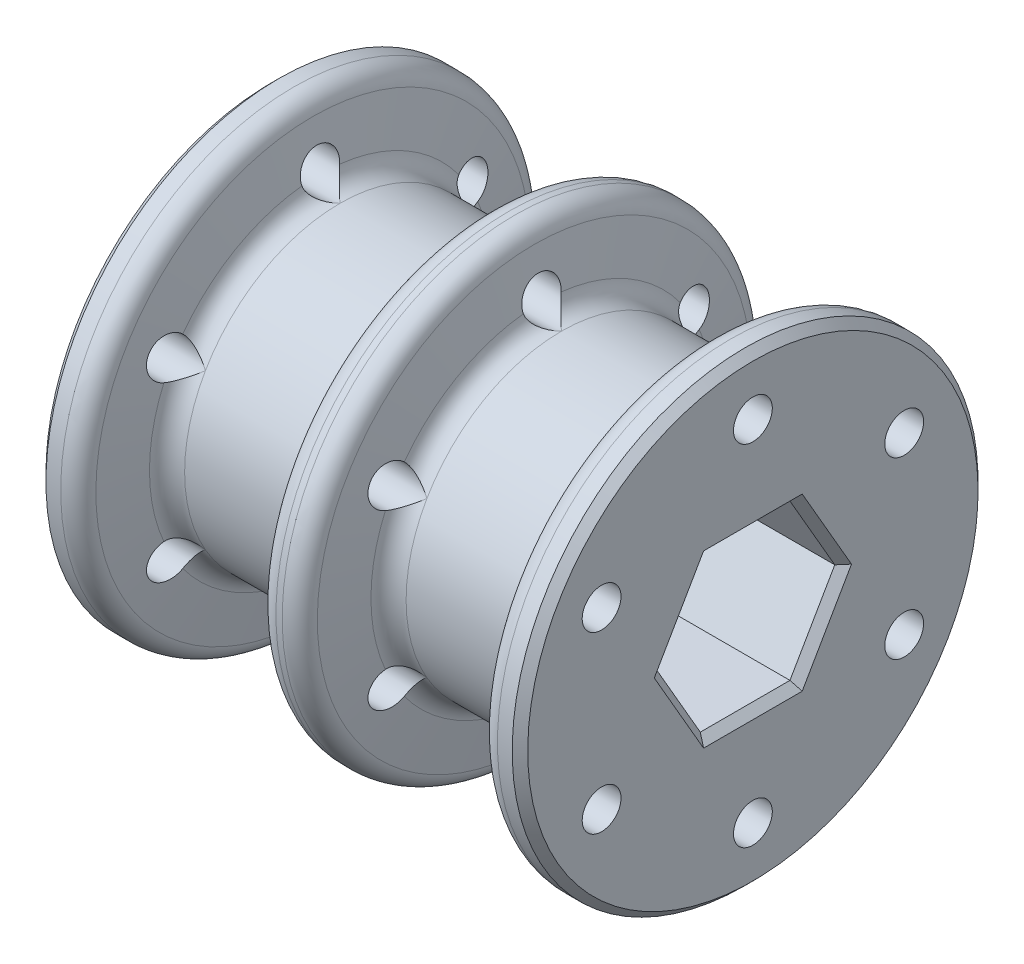
SolidWorks part; units mm, degrees
ref_plane "Front" through (0, 0, 0) normal (0, 0, 1) x (1, 0, 0)
ref_plane "Top" through (0, 0, 0) normal (0, 1, 0) x (1, 0, 0)
ref_plane "Right" through (0, 0, 0) normal (1, 0, 0) x (0, 0, -1)
sketch "Sketch1" plane through (0, 0, 0) normal (0, 0, 1) x (1, 0, 0)
  line L0 (0, 0) -> (0, 19.05)
  line L1 (0, 19.05) -> (3.175, 19.05)
  line L2 (3.175, 19.05) -> (4.2947, 12.7)
  line L3 (4.2947, 12.7) -> (16.9947, 12.7)
  line L4 (16.9947, 12.7) -> (18.1144, 19.05)
  line L5 (18.1144, 19.05) -> (21.2894, 19.05)
  line L6 (21.2894, 19.05) -> (22.409, 12.7)
  line L7 (22.409, 12.7) -> (35.109, 12.7)
  line L8 (35.109, 12.7) -> (36.2287, 19.05)
  line L9 (36.2287, 19.05) -> (39.4037, 19.05)
  line L10 (39.4037, 19.05) -> (39.4037, 0)
  line L11 (39.4037, 0) -> (0, 0)
  dimension "D1" = 3.175
  dimension "D2" = 12.7
  dimension "D3" = 100
  dimension "D4" = 100
  dimension "D5" = 19.05
  dimension "D6" = 12.7
  dimension "D7" = 39.4037
revolve "Revolve1" add sketch "Sketch1" angle 360 about L11
fillet "Fillet1" radius 1.5875 4 edges at (36.2287, 19.05, 0) (3.175, 19.05, 0) (18.1144, 19.05, 0) (21.2894, 19.05, 0)
chamfer "Chamfer1" distance 0.635 angle 45 2 edges at (0, 19.05, 0) (39.4037, 19.05, 0)
sketch "Sketch2" plane through (0, 0, 0) normal (-1, 0, 0) x (0, 0, 1)
  line L1 (7.3323, 0) -> (3.6662, 6.35)
  line L2 (3.6662, 6.35) -> (-3.6662, 6.35)
  line L3 (-3.6662, 6.35) -> (-7.3323, 0)
  line L4 (-7.3323, 0) -> (-3.6662, -6.35)
  line L5 (-3.6662, -6.35) -> (3.6662, -6.35)
  line L6 (3.6662, -6.35) -> (7.3323, 0)
  circle A0 centre (0, 0) radius 6.35 construction
  dimension "D1" = 12.7
extrude "Cut-Extrude1" cut sketch "Sketch2" against normal through all
sketch "Sketch3" plane through (0, 0, 0) normal (-1, 0, 0) x (0, 0, 1)
  line L0 (0, 0) -> (0, 14.2875) construction
  line L2 (0, 14.2875) -> (-12.3733, 7.1438) construction
  line L3 (-12.3733, 7.1438) -> (-12.3733, -7.1437) construction
  line L4 (-12.3733, -7.1437) -> (0, -14.2875) construction
  line L5 (0, -14.2875) -> (12.3733, -7.1438) construction
  line L6 (12.3733, -7.1438) -> (12.3733, 7.1437) construction
  line L7 (12.3733, 7.1437) -> (0, 14.2875) construction
  circle A0 centre (0, 14.2875) radius 1.5875 construction
  circle A1 centre (0, 0) radius 12.3733 construction
  point P4 (0, 12.7)
  dimension "D1" = 3.175
  dimension "D2" = 12.7
fillet "Fillet2" radius 1.5875 4 edges at (35.109, 12.7, 0) (22.409, 12.7, 0) (16.9947, 12.7, 0) (4.2947, 12.7, 0)
hole_wizard "1/8 (0.125) Diameter Hole1" positions "Sketch4" profile "Sketch6" hole size "1/8" standard "ANSI Inch" end condition through all
sketch "Sketch4" plane through (0, 0, 0) normal (-1, 0, 0) x (0, 0, 1)
  point P0 (0, 14.2875)
  point P3 (12.3733, 7.1437)
  point P6 (12.3733, -7.1438)
  point P9 (0, -14.2875)
  point P12 (-12.3733, -7.1437)
  point P15 (-12.3733, 7.1438)
sketch "Sketch6" plane through (0, 14.2875, 0) normal (0, 1, 0) x (0, 0, 1)
  line L0 (0, 0) -> (0, 39.4037)
  line L1 (0, 39.4037) -> (1.5875, 39.4037)
  line L2 (1.5875, 39.4037) -> (1.5875, 0)
  line L5 (1.5875, 0) -> (0, 0)
  line L11 (0, -6.35) -> (0, 107.95) construction
  dimension "Thru Hole Dia." = 3.175
  dimension "Thru Hole Depth" = 39.4037
chamfer "Chamfer2" distance 0.635 angle 45 12 edges at (39.4037, 6.35, 0) (39.4037, 3.175, 5.4993) (39.4037, -3.175, 5.4993) (39.4037, -6.35, 0) (39.4037, -3.175, -5.4993) (39.4037, 3.175, -5.4993) (0, -3.175, -5.4993) (0, -6.35, 0) (0, -3.175, 5.4993) (0, 3.175, 5.4993) (0, 6.35, 0) (0, 3.175, -5.4993)
equation "\"D4@Sketch1\"=\"D3@Sketch1\""
